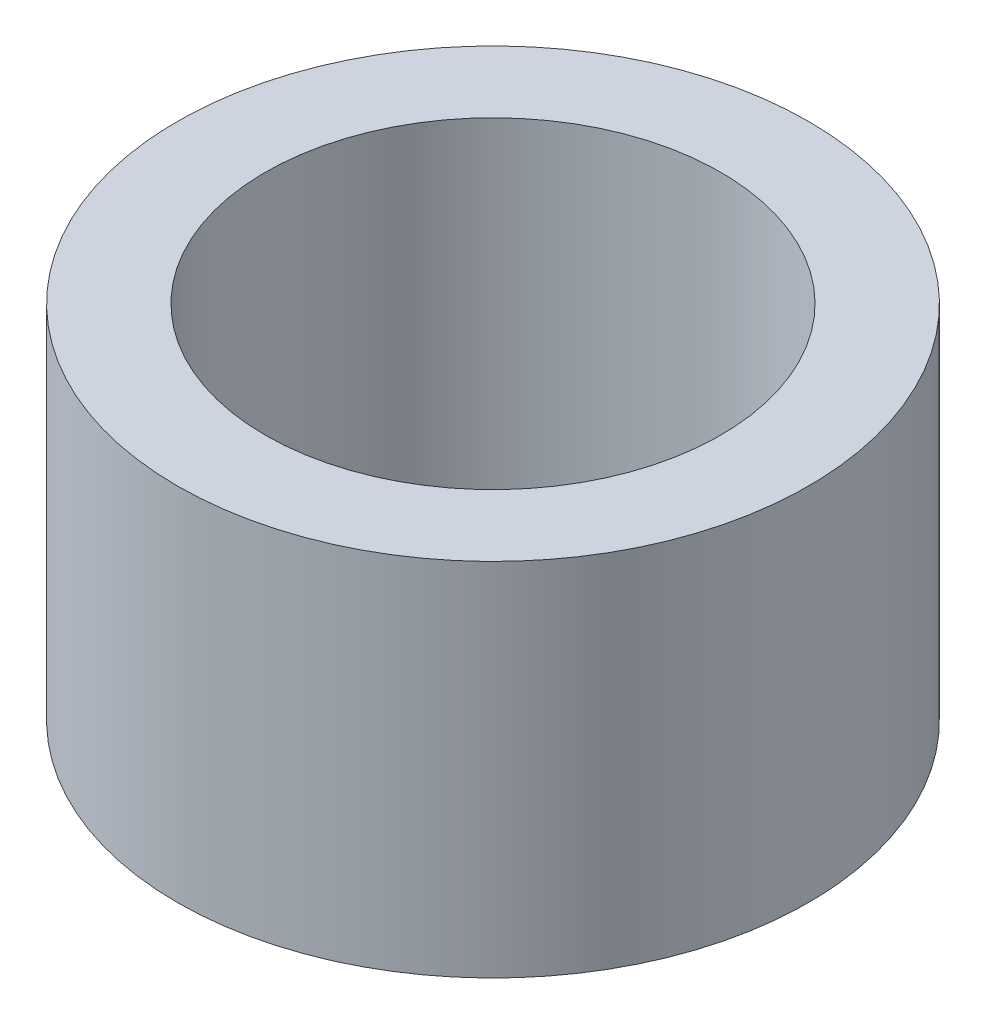
SolidWorks part; units mm, degrees
ref_plane "Front Plane" through (0, 0, 0) normal (0, 0, 1) x (1, 0, 0)
ref_plane "Top Plane" through (0, 0, 0) normal (0, 1, 0) x (1, 0, 0)
ref_plane "Right Plane" through (0, 0, 0) normal (1, 0, 0) x (0, 0, -1)
sketch "Sketch1" plane through (0, 0, 0) normal (0, 1, 0) x (1, 0, 0)
  circle A0 centre (0, 0) radius 3.5
  circle A1 centre (0, 0) radius 2.525
  dimension "D1" = 7
  dimension "D2" = 5.05
extrude "Boss-Extrude1" add sketch "Sketch1" along normal blind 4
sketch "Sketch2" [suppressed] plane through (0, 0, 0) normal (0, 1, 0) x (1, 0, 0)
  circle A0 centre (0, 0) radius 7.5
  circle A1 centre (0, 0) radius 10
  dimension "D1" = 15
  dimension "D2" = 20
extrude "Boss-Extrude2" [suppressed] add sketch "Sketch2" along normal blind 1
sketch "Sketch3" [suppressed] plane through (0, 0, 0) normal (0, 1, 0) x (1, 0, 0)
  circle A0 centre (0, 0) radius 5
  circle A1 centre (0, 0) radius 6.5
  dimension "D1" = 10
  dimension "D2" = 13
extrude "Boss-Extrude3" [suppressed] add sketch "Sketch3" along normal blind 2
